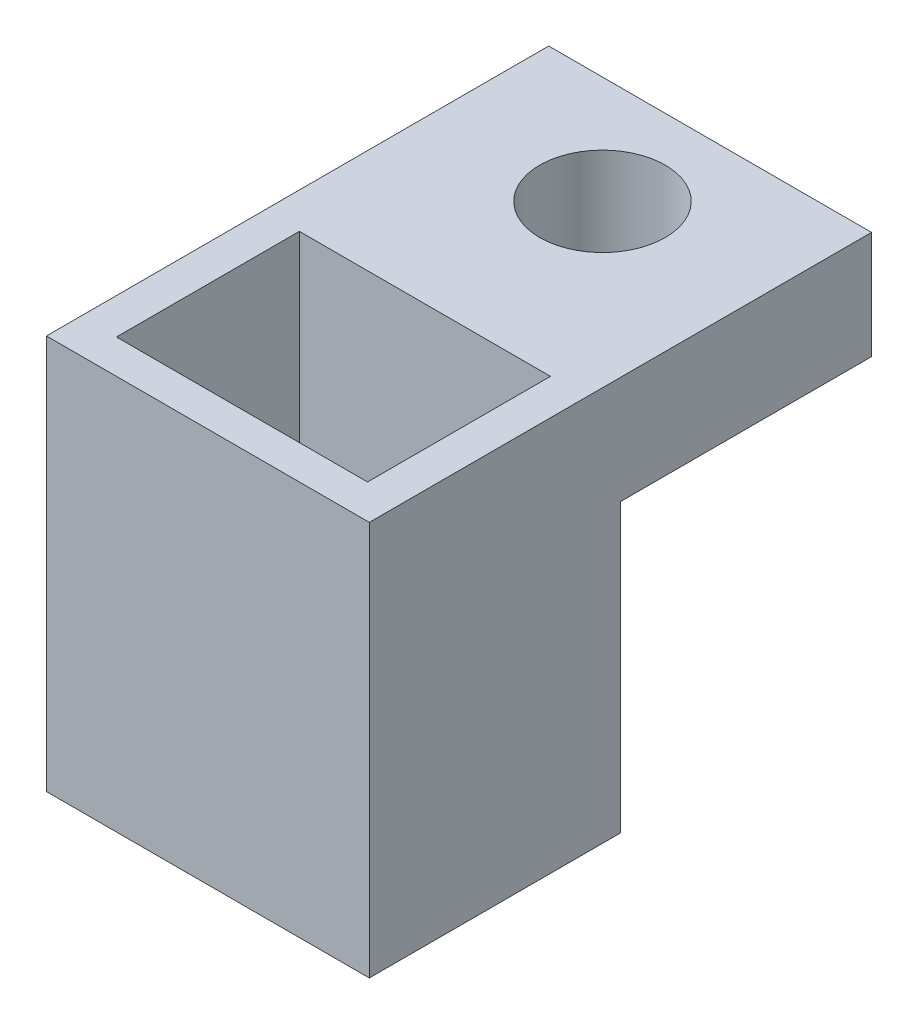
SolidWorks part; units mm, degrees
ref_plane "Front Plane" through (0, 0, 0) normal (0, 0, 1) x (1, 0, 0)
ref_plane "Top Plane" through (0, 0, 0) normal (0, 1, 0) x (1, 0, 0)
ref_plane "Right Plane" through (0, 0, 0) normal (1, 0, 0) x (0, 0, -1)
sketch "Sketch4" plane through (0, 0, 0) normal (1, 0, 0) x (0, 0, -1)
  line L0 (0, 0) -> (0, -8)
  line L1 (0, -8) -> (-7, -8)
  line L2 (-7, -8) -> (-7, 3)
  line L3 (-7, 3) -> (7, 3)
  line L4 (7, 3) -> (7, 0)
  line L5 (7, 0) -> (0, 0)
  dimension "D1" = 8
  dimension "D2" = 3
  dimension "D3" = 7
  dimension "D4" = 7
extrude "Boss-Extrude2" add sketch "Sketch4" along normal blind 9
sketch "Sketch6" plane through (0, 3, 0) normal (0, 1, 0) x (1, 0, 0)
  line L0 (4.5, 7) -> (4.5, -7) construction
  line L1 (9, 7) -> (0, 7) construction
  line L2 (9, -7) -> (0, -7) construction
  line L4 (1, -0.95) -> (8, -0.95)
  line L5 (1, -0.95) -> (1, -6.05)
  line L6 (1, -6.05) -> (8, -6.05)
  line L7 (8, -0.95) -> (8, -6.05)
  circle A0 centre (4.5, 4) radius 1.75
  point P12 (8, -3.5)
  dimension "D1" = 3.5
  dimension "D2" = 3.5
  dimension "D3" = 5.1
  dimension "D4" = 3.5
  dimension "D5" = 3.5
  dimension "D6" = 3
extrude "Cut-Extrude1" cut sketch "Sketch6" against normal through all
equation "\"D4@Sketch6\"=\"D2@Sketch6\""
